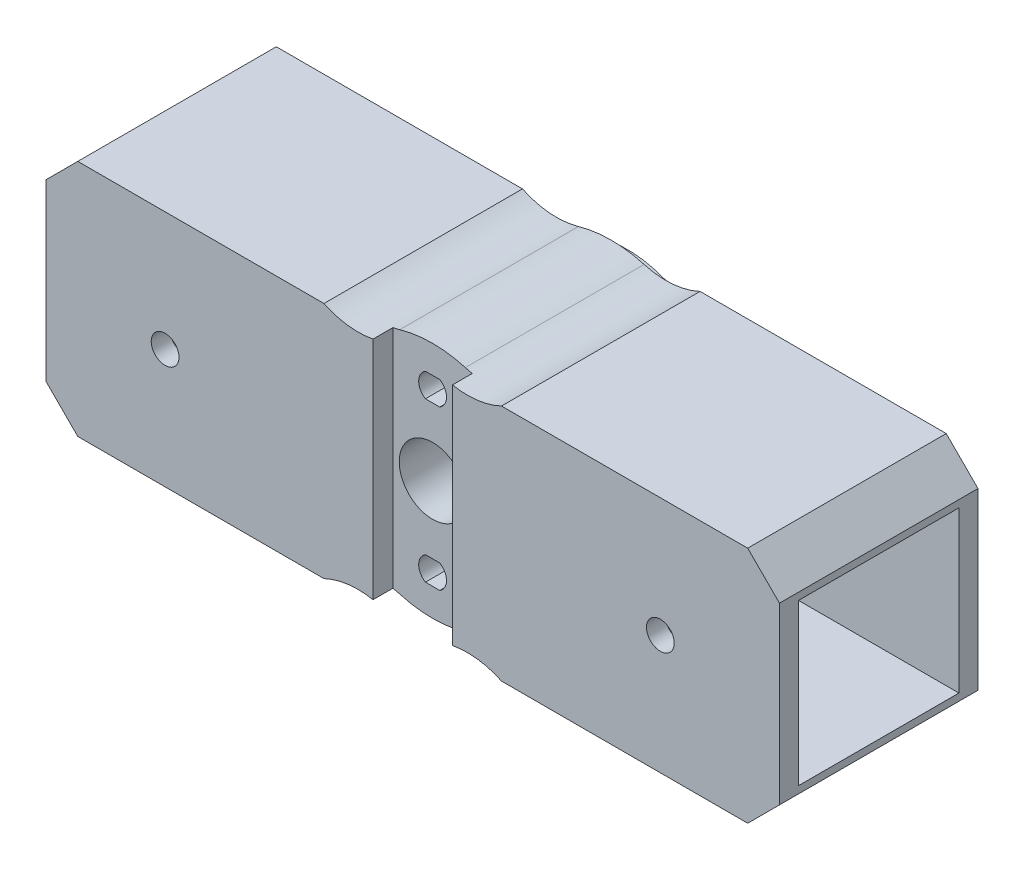
SolidWorks part; units mm, degrees
ref_plane "Alzado" through (0, 0, 0) normal (0, 0, 1) x (1, 0, 0)
ref_plane "Planta" through (0, 0, 0) normal (0, 1, 0) x (1, 0, 0)
ref_plane "Vista lateral" through (0, 0, 0) normal (1, 0, 0) x (0, 0, -1)
sketch "Croquis1" plane through (0, 0, 0) normal (0, 0, 1) x (1, 0, 0)
  circle A0 centre (0, 0) radius 15
  circle A1 centre (0, 0) radius 11.1
  dimension "D1" = 30
  dimension "D2" = 22.2
extrude "Saliente-Extruir1" add sketch "Croquis1" along normal mid plane 25
sketch "Croquis10" plane through (0, 0, 12.5) normal (0, 0, 1) x (1, 0, 0)
  line L0 (11.1803, 0) -> (-11.1803, 0) construction
  line L1 (0, 0) -> (0, 10.6419) construction
  line L2 (-11.1803, -15) -> (-11.1803, 15)
  line L3 (-11.1803, 15) -> (-46.1803, 15)
  line L4 (-46.1803, 15) -> (-46.1803, -15)
  line L5 (-46.1803, -15) -> (-11.1803, -15)
  line L6 (46.1803, 15) -> (46.1803, -15)
  line L7 (11.1803, 15) -> (46.1803, 15)
  line L8 (11.1803, -15) -> (11.1803, 15)
  line L9 (46.1803, -15) -> (11.1803, -15)
  line L10 (-11.1803, 0) -> (-46.1803, 0) construction
  circle A1 centre (-31.1803, 0) radius 1.75
  circle A2 centre (31.1803, 0) radius 1.75
  point P5 (0, 0)
  point P13 (-11.1803, 0)
  dimension "D3" = 3.5
  dimension "D1" = 35
  dimension "D2" = 30
  dimension "D4" = 15
extrude "Saliente-Extruir8" add sketch "Croquis10" against normal blind 25
sketch "Croquis11" plane through (0, 0, -12.5) normal (0, 0, 1) x (1, 0, 0)
  line L6 (0, 0) -> (0, 7.4469) construction
  line L7 (16.1803, -10) -> (36.1803, -10)
  line L8 (16.1803, 10) -> (16.1803, -10)
  line L9 (36.1803, 10) -> (16.1803, 10)
  line L10 (36.1803, -10) -> (36.1803, 10)
  dimension "D1" = 20
extrude "Cortar-Extruir1" [suppressed] cut sketch "Croquis11" along normal blind 10
sketch "Croquis12" plane through (0, 0, 12.5) normal (0, 0, 1) x (1, 0, 0)
  line L0 (-46.1803, 15) -> (-26.1803, 15)
  line L1 (-11.1803, 15) -> (-46.1803, 15) construction
  line L2 (-26.1803, 15) -> (-26.1803, -15)
  line L3 (-46.1803, -15) -> (-11.1803, -15) construction
  line L4 (-26.1803, -15) -> (-46.1803, -15)
  line L5 (-46.1803, -15) -> (-46.1803, 15)
  dimension "D1" = 20
extrude "Cortar-Extruir2" [suppressed] cut sketch "Croquis12" against normal blind 10
sketch "Croquis13" plane through (0, 0, 12.5) normal (0, 0, 1) x (1, 0, 0)
  circle A0 centre (0, 0) radius 11.1
  circle A1 centre (0, 0) radius 4.2
  dimension "D1" = 22.2
  dimension "D2" = 8.4
extrude "Saliente-Extruir9" add sketch "Croquis13" against normal blind 12.8
sketch "Croquis14" plane through (0, 0, -12.5) normal (0, 0, -1) x (-1, 0, 0)
  circle A0 centre (0, 0) radius 11.1
  circle A1 centre (0, 0) radius 13
  dimension "D1" = 22.2
  dimension "D2" = 26
extrude "Saliente-Extruir10" add sketch "Croquis14" along normal blind 2
sketch "Croquis15" plane through (0, 0, 12.5) normal (0, 0, 1) x (1, 0, 0)
  line L0 (-5, 0) -> (-5, 15)
  line L1 (-5, 15) -> (5, 15)
  line L2 (5, 15) -> (5, -15)
  line L3 (5, -15) -> (-5, -15)
  line L4 (-5, -15) -> (-5, 0)
  point P3 (0, 15)
  dimension "D1" = 10
  dimension "D2" = 30
extrude "Cortar-Extruir3" cut sketch "Croquis15" against normal blind 2.5
sketch "Croquis16" plane through (0, 0, 10) normal (0, 0, 1) x (1, 0, 0)
  line L0 (0, 15) -> (0, 10) construction
  line L1 (0, 10) -> (0, 0) construction
  line L2 (0, 0) -> (0, -10) construction
  line L3 (0, -10) -> (0, -15) construction
  line L4 (-0.9014, 11.5) -> (0.9014, 11.5)
  line L5 (-0.9014, 8.5) -> (0.9014, 8.5)
  line L6 (0, 0) -> (-3.0161, 0) construction
  line L7 (-0.9014, -8.5) -> (0.9014, -8.5)
  line L8 (-0.9014, -11.5) -> (0.9014, -11.5)
  arc A0 (5, 14.1421) -> (-5, 14.1421) centre (0, 0) ccw construction
  arc A1 (-5, -14.1421) -> (5, -14.1421) centre (0, 0) ccw construction
  arc A2 (-0.9014, 11.5) -> (-0.9014, 8.5) centre (0, 10) ccw
  arc A3 (0.9014, 8.5) -> (0.9014, 11.5) centre (0, 10) ccw
  arc A4 (-0.9014, -11.5) -> (-0.9014, -8.5) centre (0, -10) cw
  arc A5 (0.9014, -8.5) -> (0.9014, -11.5) centre (0, -10) cw
  point P16 (0, 11.5)
  point P19 (0, 8.5)
  dimension "D2" = 3.5
  dimension "D1" = 5
  dimension "D3" = 3
extrude "Cortar-Extruir4" cut sketch "Croquis16" against normal blind 7.5
sketch "Croquis17" plane through (-46.1803, 0, 0) normal (-1, 0, 0) x (0, 0, 1)
  line L1 (10.1, 10.1) -> (-10.1, 10.1)
  line L2 (10.1, 10.1) -> (10.1, -10.1)
  line L3 (10.1, -10.1) -> (-10.1, -10.1)
  line L4 (-10.1, 10.1) -> (-10.1, -10.1)
  line L5 (10.1, 10.1) -> (-10.1, -10.1) construction
  line L6 (10.1, -10.1) -> (-10.1, 10.1) construction
  point P0 (0, 0)
  dimension "D1" = 20.2
  dimension "D2" = 20.2
extrude "Cortar-Extruir5" cut sketch "Croquis17" against normal blind 30
mirror "Simetría1" about plane through (0, 0, 0) normal (1, 0, 0) of "Cortar-Extruir5"
fillet "Redondeo1" radius 10 4 edges at (-11.1803, 10, 0) (11.1803, 10, 0) (-11.1803, -10, 0) (11.1803, -10, 0)
chamfer "Chaflán1" distance 4 angle 45 4 edges at (46.1803, 15, 0) (46.1803, -15, 0) (-46.1803, 15, 0) (-46.1803, -15, 0)
